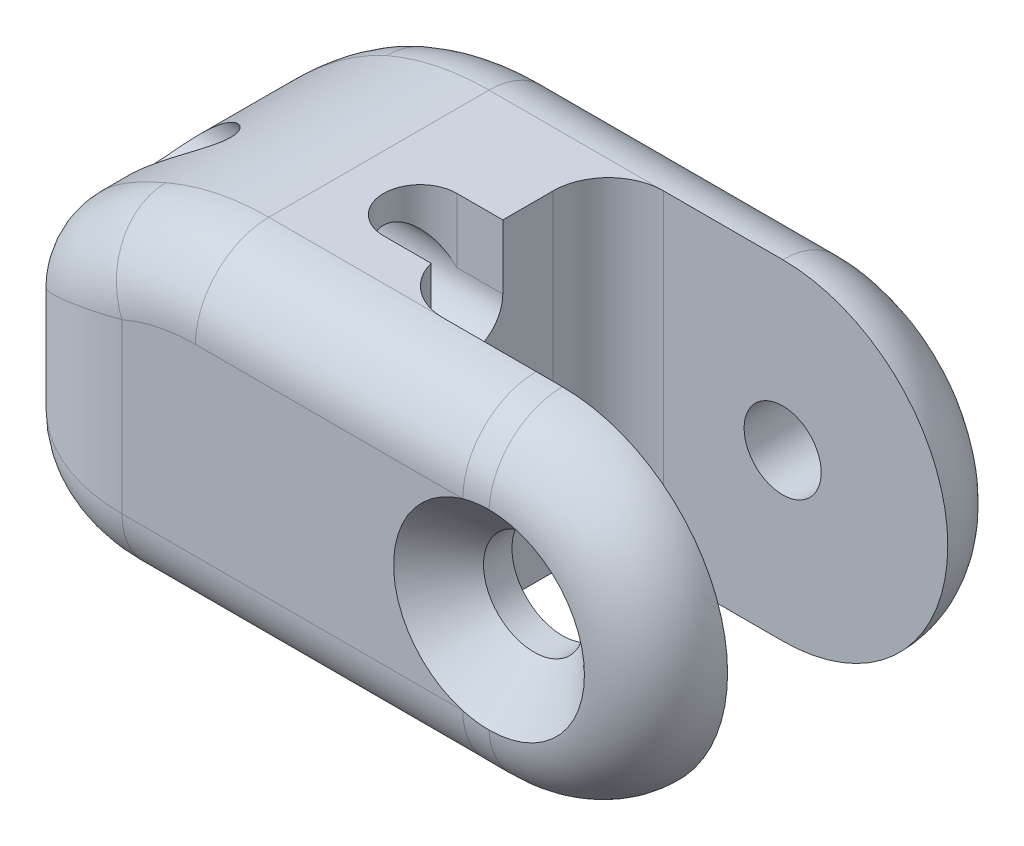
SolidWorks part; units mm, degrees
ref_plane "Front Plane" through (0, 0, 0) normal (0, 0, 1) x (1, 0, 0)
ref_plane "Top Plane" through (0, 0, 0) normal (0, 1, 0) x (1, 0, 0)
ref_plane "Right Plane" through (0, 0, 0) normal (1, 0, 0) x (0, 0, -1)
sketch "Sketch2" plane through (0, 0, 0) normal (0, 1, 0) x (1, 0, 0)
  line L0 (-5.5, 10) -> (23.5, 10)
  line L1 (23.5, 10) -> (23.5, 6)
  line L2 (23.5, 6) -> (8, 6)
  line L3 (5, 3) -> (5, -3)
  line L4 (8, -6) -> (23.5, -6)
  line L5 (23.5, -6) -> (23.5, -10)
  line L8 (-49.3622, 0) -> (56.3776, 0) construction
  line L9 (0, 21.2372) -> (0, -19.0689) construction
  line L10 (5, 3) -> (8, 3) construction
  line L11 (8, 3) -> (8, 6) construction
  line L16 (-5.5, -10) -> (23.5, -10)
  arc A0 (8, 6) -> (5, 3) centre (8, 3) ccw
  arc A1 (8, -6) -> (5, -3) centre (8, -3) cw
  arc A3 (-5.5, 10) -> (-5.5, -10) centre (-5.5, 0) ccw
  point P13 (8, 3)
  dimension "D2" = 20
  dimension "D3" = 4
  dimension "D4" = 18.5
  dimension "D5" = 12
  dimension "D6" = 3
  dimension "D7" = 3
  dimension "D8" = 5
  dimension "D9" = 29
extrude "Boss-Extrude1" add sketch "Sketch2" along normal blind 18
sketch "Sketch5" plane through (0, 0, 10) normal (0, 0, 1) x (1, 0, 0)
  line L0 (-13.5058, 9) -> (31.8434, 9) construction
  line L1 (-5.5, 18) -> (-5.5, 0) construction
  line L2 (23.5, 18) -> (23.5, 0) construction
  line L3 (-5.5, 18) -> (23.5, 18) construction
  line L4 (14.5, 18) -> (14.5, 0) construction
  line L5 (-15.5, 0) -> (-5.5, 0) construction
  line L7 (-15.5, 0) -> (-15.5, 4)
  line L8 (-15.5, 0) -> (14.5, 0)
  line L9 (-1.5, 18) -> (14.5, 18)
  arc A1 (14.5, 0) -> (14.5, 18) centre (14.5, 9) ccw
  arc A2 (-1.5, 18) -> (-15.5, 4) centre (-1.5, 4) ccw
  dimension "D2" = 4
  dimension "D1" = 9
  dimension "D3" = 10
extrude "Cut-Extrude1" cut sketch "Sketch5" against normal blind 20 flip side to cut
sketch "Sketch6" plane through (0, 0, 10) normal (0, 0, 1) x (1, 0, 0)
  line L0 (14.5, 0) -> (14.5, 18) construction
  point P4 (14.5, 9)
hole_wizard "CSK for M5 Countersunk Flat Head Screw1" positions "Sketch7" profile "Sketch8" countersink size "M5" standard "DIN" end condition up to next
sketch "Sketch7" plane through (0, 0, 10) normal (0, 0, 1) x (1, 0, 0)
  point P0 (14.5, 9)
sketch "Sketch8" plane through (14.5, 9, 10) normal (1, 0, 0) x (0, -1, 0)
  line L0 (0, 0) -> (0, 4)
  line L1 (0, 4) -> (2.75, 4)
  line L2 (2.75, 4) -> (2.75, 2.45)
  line L3 (2.75, 2.45) -> (5.2, 0)
  line L5 (5.2, 0) -> (0, 0)
  line L6 (-2.75, 2.45) -> (-5.2, 0) construction
  line L11 (0, -6.35) -> (0, 107.95) construction
  dimension "Thru Hole Dia." = 5.5
  dimension "Thru Hole Depth" = 4
  dimension "Near C'Sink Dia." = 10.4
  dimension "Near C'Sink Angle" = 90
hole_wizard "M5 Tapped Hole1" positions "Sketch9" profile "Sketch11" tap size "M5" standard "DIN" end condition through all
sketch "Sketch9" plane through (0, 0, 10) normal (0, 0, 1) x (1, 0, 0)
  point P0 (14.5, 9)
sketch "Sketch11" plane through (14.5, 9, 10) normal (1, 0, 0) x (0, -1, 0)
  line L0 (0, 0) -> (0, 20)
  line L1 (0, 20) -> (2.1, 20)
  line L2 (2.1, 20) -> (2.1, 3.1)
  line L3 (2.1, 3.1) -> (5.2, 0)
  line L5 (5.2, 0) -> (0, 0)
  line L6 (-2.1, 3.1) -> (-5.2, 0) construction
  line L11 (0, -6.35) -> (0, 107.95) construction
  dimension "Thru Tap Drill Dia." = 4.2
  dimension "Thru Tap Drill Depth" = 20
  dimension "Near C'Sink Dia." = 10.4
  dimension "Near C'Sink Angle" = 90
cosmetic thread "Hole Thread1" parameters "D2"=5
fillet "Fillet2" radius 4 11 edges at (-11.0658, 14.2223, -8.308) (-3.5212, 17.8533, -10) (6.5, 18, -10) (23.5, 9, -10) (-11.0658, 14.2223, 8.308) (-3.5212, 17.8533, 10) (6.5, 18, 10) (23.5, 9, 10) (4.5, 0, 10) (-15.5, 0, 0) (4.5, 0, -10)
sketch "Sketch13" plane through (5, 0, 0) normal (1, 0, 0) x (0, 0, -1)
  line L0 (-1.75, -2.2721) -> (-1.75, 20.0856) construction
  line L1 (-3, 0) -> (3, 0) construction
  line L2 (-3, 18) -> (3, 18) construction
  circle A0 centre (-1.75, 14.5) radius 2
  point P4 (0, 0)
  dimension "D2" = 3.5
  dimension "D3" = 4
  dimension "D1" = 1.75
extrude "Cut-Extrude2" cut sketch "Sketch13" against normal through all both and the other way through all
sketch "Sketch14" plane through (0, 18, 0) normal (0, 1, 0) x (1, 0, 0)
  line L0 (5, 0) -> (-14.1432, 0) construction
  line L3 (5, -3) -> (5, 3) construction
  line L4 (2.5, -3.75) -> (7.4532, -3.75)
  line L5 (2.5, 0.25) -> (7.4532, 0.25)
  line L6 (7.4532, 0.25) -> (7.4532, -3.75)
  arc A0 (2.5, 0.25) -> (2.5, -3.75) centre (2.5, -1.75) ccw
  dimension "D1" = 1.75
  dimension "D2" = 2.5
extrude "Cut-Extrude3" cut sketch "Sketch14" against normal blind 3.5
